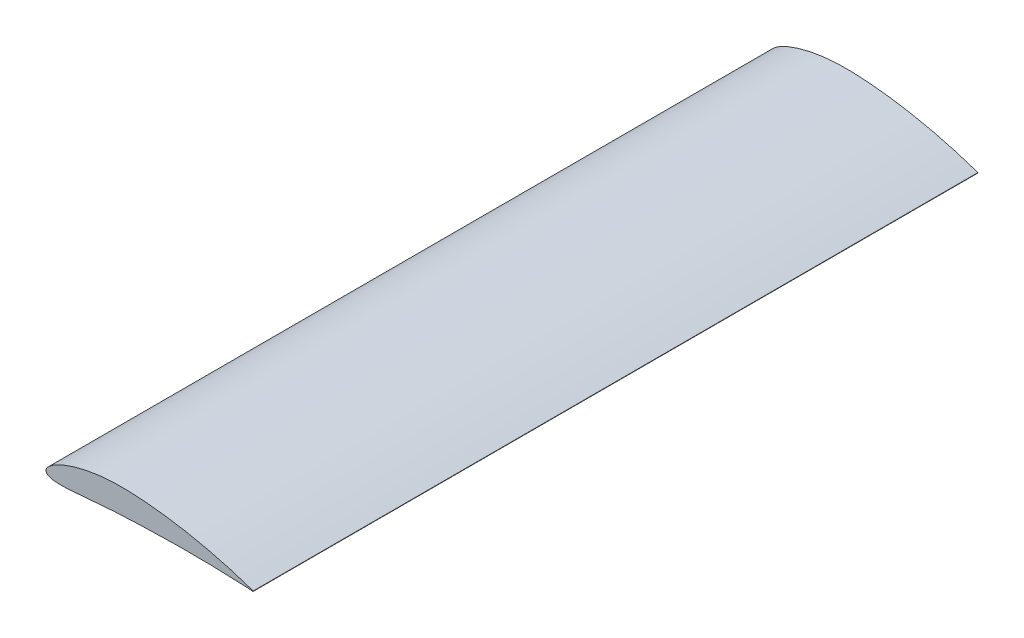
SolidWorks part; units mm, degrees
ref_plane "Front Plane" through (0, 0, 0) normal (0, 0, 1) x (1, 0, 0)
ref_plane "Top Plane" through (0, 0, 0) normal (0, 1, 0) x (1, 0, 0)
ref_plane "Right Plane" through (0, 0, 0) normal (1, 0, 0) x (0, 0, -1)
curve "Curve2"
  spline degree 3 poles (1000.25, 1.24, 0) (999.36, 1.5466, 0) (995.8139, 2.7683, 0) (987.8762, 5.5077, 0) (974.7136, 9.9275, 0) (956.465, 15.9446, 0) (933.2861, 23.3123, 0) (905.3935, 31.8009, 0) (873.0611, 41.1442, 0) (836.5996, 51.0483, 0) (796.3762, 61.2143, 0) (752.7953, 71.3209, 0) (706.3231, 81.1144, 0) (657.4446, 90.2776, 0) (606.6871, 98.541, 0) (554.6079, 105.6901, 0) (501.792, 111.4952, 0) (448.8062, 115.7722, 0) (395.8896, 118.5809, 0) (343.6082, 118.9114, 0) (292.6925, 116.357, 0) (244.199, 111.1728, 0) (198.7693, 103.6648, 0) (157.0012, 94.1608, 0) (119.4181, 83.1247, 0) (86.4596, 71.0512, 0) (58.48, 58.4287, 0) (35.7445, 45.7437, 0) (18.354, 33.4445, 0) (6.4016, 21.7983, 0) (-0.4785, 10.7687, 0) (-1.1021, -0.3322, 0) (5.4783, -9.2258, 0) (17.0143, -14.7948, 0) (32.8747, -18.4511, 0) (53.3085, -20.3675, 0) (78.1118, -20.7512, 0) (107.0475, -19.7633, 0) (139.7896, -17.6475, 0) (176.0022, -14.654, 0) (215.3329, -11.125, 0) (257.4273, -7.3624, 0) (301.9209, -3.6922, 0) (348.4441, -0.4557, 0) (396.9816, 1.9832, 0) (447.1013, 3.7059, 0) (498.2783, 5.4818, 0) (549.6221, 6.9005, 0) (600.5599, 7.9279, 0) (650.5484, 8.5041, 0) (699.0372, 8.6069, 0) (745.4858, 8.2663, 0) (789.3705, 7.5598, 0) (830.1852, 6.5089, 0) (867.4516, 5.2968, 0) (900.7439, 3.9432, 0) (929.5972, 2.6539, 0) (953.857, 1.2862, 0) (972.6764, 0.624, 0) (987.1696, -1.0584, 0) (994.3521, -0.0144, 0) (999.8798, -2.0481, 0) (999.9716, -0.4847, 0) (1000, 0, 0) knots 0 0 0 0 0.001372 0.005465 0.012235 0.021602 0.033461 0.047671 0.064081 0.082496 0.102719 0.124527 0.147676 0.171913 0.196978 0.222597 0.248497 0.274385 0.300041 0.32569 0.350525 0.37428 0.396711 0.417577 0.436654 0.453744 0.46868 0.481329 0.491631 0.499616 0.505546 0.510185 0.514824 0.520702 0.528516 0.538466 0.550543 0.564643 0.580638 0.598345 0.617584 0.638174 0.659922 0.682632 0.706121 0.730727 0.7557 0.780732 0.805564 0.829932 0.85357 0.876213 0.89761 0.917519 0.935698 0.951943 0.966047 0.97784 0.987174 0.993932 0.998018 0.999386 1 1 1 1
sketch "Sketch1" plane through (0, 0, 0) normal (0, 0, 1) x (1, 0, 0)
  arc A0 (1000.25, 1.24) -> (1000, 0) centre (1000.0422, 0.6367) cw
  spline S0 degree 3 poles (1071.3958, -1956.545) (1436.9332, -141.2985) (1213.3722, -72.3137) (987.8762, 5.5077) (974.7136, 9.9275) (956.465, 15.9446) (933.2861, 23.3123) (905.3935, 31.8009) (873.0611, 41.1442) (836.5996, 51.0483) (796.3762, 61.2143) (752.7953, 71.3209) (706.3231, 81.1144) (657.4446, 90.2776) (606.6871, 98.541) (554.6079, 105.6901) (501.792, 111.4952) (448.8062, 115.7722) (395.8896, 118.5809) (343.6082, 118.9114) (292.6925, 116.357) (244.199, 111.1728) (198.7693, 103.6648) (157.0012, 94.1608) (119.4181, 83.1247) (86.4596, 71.0512) (58.48, 58.4287) (35.7445, 45.7437) (18.354, 33.4445) (6.4016, 21.7983) (-0.4785, 10.7687) (-1.1021, -0.3322) (5.4783, -9.2258) (17.0143, -14.7948) (32.8747, -18.4511) (53.3085, -20.3675) (78.1118, -20.7512) (107.0475, -19.7633) (139.7896, -17.6475) (176.0022, -14.654) (215.3329, -11.125) (257.4273, -7.3624) (301.9209, -3.6922) (348.4441, -0.4557) (396.9816, 1.9832) (447.1013, 3.7059) (498.2783, 5.4818) (549.6221, 6.9005) (600.5599, 7.9279) (650.5484, 8.5041) (699.0372, 8.6069) (745.4858, 8.2663) (789.3705, 7.5598) (830.1852, 6.5089) (867.4516, 5.2968) (900.7439, 3.9432) (929.5972, 2.6539) (953.857, 1.2862) (972.6764, 0.624) (987.1696, -1.0584) (994.3521, -0.0144) (1010.8156, -6.0714) (938.1956, 100.2197) (2230.5974, -1569.3283) knots -0.335333 -0.335333 -0.335333 -0.335333 0.001372 0.005465 0.012235 0.021602 0.033461 0.047671 0.064081 0.082496 0.102719 0.124527 0.147676 0.171913 0.196978 0.222597 0.248497 0.274385 0.300041 0.32569 0.350525 0.37428 0.396711 0.417577 0.436654 0.453744 0.46868 0.481329 0.491631 0.499616 0.505546 0.510185 0.514824 0.520702 0.528516 0.538466 0.550543 0.564643 0.580638 0.598345 0.617584 0.638174 0.659922 0.682632 0.706121 0.730727 0.7557 0.780732 0.805564 0.829932 0.85357 0.876213 0.89761 0.917519 0.935698 0.951943 0.966047 0.97784 0.987174 0.993932 0.998018 0.999386 1.012006 1.012006 1.012006 1.012006 only from (1000.25, 1.24) to (1000, 0) construction
  spline S1 degree 3 poles (1000.25, 1.24) (999.36, 1.5466) (995.8139, 2.7683) (987.8762, 5.5077) (974.7136, 9.9275) (956.465, 15.9446) (933.2861, 23.3123) (905.3935, 31.8009) (873.0611, 41.1442) (836.5996, 51.0483) (796.3762, 61.2143) (752.7953, 71.3209) (706.3231, 81.1144) (657.4446, 90.2776) (606.6871, 98.541) (554.6079, 105.6901) (501.792, 111.4952) (448.8062, 115.7722) (395.8896, 118.5809) (343.6082, 118.9114) (292.6925, 116.357) (244.199, 111.1728) (198.7693, 103.6648) (157.0012, 94.1608) (119.4181, 83.1247) (86.4596, 71.0512) (58.48, 58.4287) (35.7445, 45.7437) (18.354, 33.4445) (6.4016, 21.7983) (-0.4785, 10.7687) (-1.1021, -0.3322) (5.4783, -9.2258) (17.0143, -14.7948) (32.8747, -18.4511) (53.3085, -20.3675) (78.1118, -20.7512) (107.0475, -19.7633) (139.7896, -17.6475) (176.0022, -14.654) (215.3329, -11.125) (257.4273, -7.3624) (301.9209, -3.6922) (348.4441, -0.4557) (396.9816, 1.9832) (447.1013, 3.7059) (498.2783, 5.4818) (549.6221, 6.9005) (600.5599, 7.9279) (650.5484, 8.5041) (699.0372, 8.6069) (745.4858, 8.2663) (789.3705, 7.5598) (830.1852, 6.5089) (867.4516, 5.2968) (900.7439, 3.9432) (929.5972, 2.6539) (953.857, 1.2862) (972.6764, 0.624) (987.1696, -1.0584) (994.3521, -0.0144) (999.8798, -2.0481) (999.9716, -0.4847) (1000, 0) knots 0 0 0 0 0.001372 0.005465 0.012235 0.021602 0.033461 0.047671 0.064081 0.082496 0.102719 0.124527 0.147676 0.171913 0.196978 0.222597 0.248497 0.274385 0.300041 0.32569 0.350525 0.37428 0.396711 0.417577 0.436654 0.453744 0.46868 0.481329 0.491631 0.499616 0.505546 0.510185 0.514824 0.520702 0.528516 0.538466 0.550543 0.564643 0.580638 0.598345 0.617584 0.638174 0.659922 0.682632 0.706121 0.730727 0.7557 0.780732 0.805564 0.829932 0.85357 0.876213 0.89761 0.917519 0.935698 0.951943 0.966047 0.97784 0.987174 0.993932 0.998018 0.999386 1 1 1 1
extrude "Boss-Extrude1" add sketch "Sketch1" along normal blind 7000 contours S1 A0
scale "Scale1" bodies to scale 101 scale about origin uniform scaling no x scale factor 2 y scale factor 2 z scale factor 1
ref_axis "Axis1" through (2000.5, 2.48, 7000) along (0, 0, -1)
ref_plane "Plane1" through (2000.5, 0, 0) normal (1, 0, 0) x (0, 0, -1)
sketch "Sketch2" plane through (0, 0, 7000) normal (0, 0, 1) x (1, 0, 0)
  line L0 (0, 0) -> (2000.5, 2.48)
ref_axis "Axis2" through (-4598.815, -5.7011, 7000) along (1, 0.0012, 0)
ref_point "Point1"
ref_plane "Plane2" through (0, 0, 7000) normal (0, 0, -1) x (1, 0.0012, 0)
ref_plane "Plane4" through (0, 0, 6000) normal (0, 0, -1) x (1, 0.0012, 0)
ref_axis "Axis3" through (2101.5387, 0, 6000) along (-1, 0, 0)
ref_point "Point2"
ref_plane "Plane5" through (0, 0, 1000) normal (0, 0, -1) x (1, 0.0012, 0)
ref_axis "Axis4" through (2101.5387, 0, 1000) along (-1, 0, 0)
ref_point "Point3"
ref_plane "Plane6" through (1600.5, 0, 0) normal (1, 0, 0) x (0, 0, -1)
ref_point "Point4"
ref_point "Point5"
